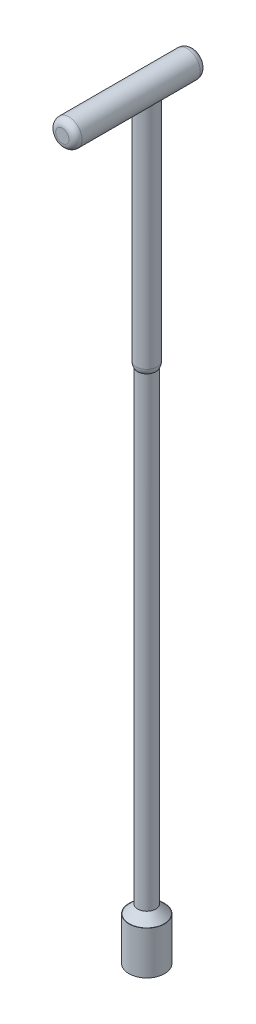
SolidWorks part; units mm, degrees
ref_plane "Front Plane" through (0, 0, 0) normal (0, 0, 1) x (1, 0, 0)
ref_plane "Top Plane" through (0, 0, 0) normal (0, 1, 0) x (1, 0, 0)
ref_plane "Right Plane" through (0, 0, 0) normal (1, 0, 0) x (0, 0, -1)
sketch "Sketch1" plane through (0, 0, 0) normal (0, 1, 0) x (1, 0, 0)
  circle A0 centre (0, 0) radius 19
  dimension "D1" = 38
extrude "Boss-Extrude1" add sketch "Sketch1" along normal blind 46
sketch "Sketch2" plane through (0, 46, 0) normal (0, 1, 0) x (1, 0, 0)
  circle A0 centre (0, 0) radius 9.65
  dimension "D1" = 19.3
extrude "Boss-Extrude2" add sketch "Sketch2" along normal blind 505
sketch "Sketch3" plane through (0, 551, 0) normal (0, 1, 0) x (1, 0, 0)
  circle A0 centre (0, 0) radius 11.15
  dimension "D1" = 22.3
extrude "Boss-Extrude3" add sketch "Sketch3" along normal blind 250
chamfer "Chamfer1" distance 9 angle 45 1 edges at (0, 46, 9.65)
fillet "Fillet1" radius 10 1 edges at (0, 551, 11.15)
sketch "Sketch4" plane through (0, 0, 0) normal (0, 0, 1) x (1, 0, 0)
  circle A0 centre (0, 809) radius 14.05
  dimension "D1" = 28.1
extrude "Boss-Extrude4" add sketch "Sketch4" along normal blind 90 and the other way blind 50
fillet "Fillet2" radius 7 2 edges at (14.05, 809, -50) (14.05, 809, 90)
